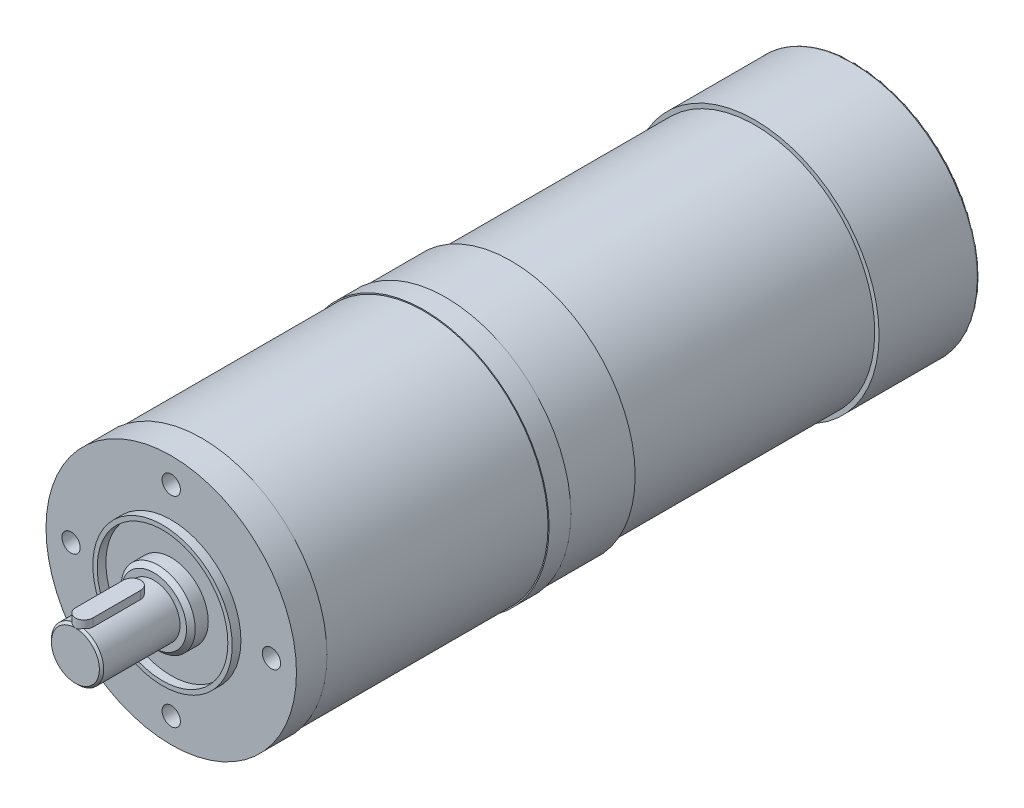
SolidWorks part; units mm, degrees
ref_plane "Plan de face" through (0, 0, 0) normal (0, 0, 1) x (1, 0, 0)
ref_plane "Plan de dessus" through (0, 0, 0) normal (0, 1, 0) x (1, 0, 0)
ref_plane "Plan de droite" through (0, 0, 0) normal (1, 0, 0) x (0, 0, -1)
sketch "Esquisse1" plane through (0, 0, 0) normal (0, 0, 1) x (1, 0, 0)
  circle A0 centre (0, 0) radius 28.5
  dimension "D1" = 57
extrude "Boss.-Extru.1" add sketch "Esquisse1" along normal blind 23
sketch "Esquisse3" plane through (0, 0, 23) normal (0, 0, 1) x (1, 0, 0)
  circle A0 centre (0, 0) radius 27.5
  dimension "D1" = 55
extrude "Boss.-Extru.2" add sketch "Esquisse3" along normal blind 56
sketch "Esquisse4" plane through (0, 0, 79) normal (0, 0, 1) x (1, 0, 0)
  circle A0 centre (0, 0) radius 28.5
  dimension "D1" = 57
extrude "Boss.-Extru.3" add sketch "Esquisse4" along normal blind 15
sketch "Esquisse5" plane through (0, 0, 94) normal (0, 0, 1) x (1, 0, 0)
  circle A0 centre (0, 0) radius 28.75
  dimension "D1" = 57.5
extrude "Boss.-Extru.4" add sketch "Esquisse5" along normal blind 5
sketch "Esquisse6" plane through (0, 0, 99) normal (0, 0, 1) x (1, 0, 0)
  circle A0 centre (0, 0) radius 28.5
  dimension "D1" = 57
extrude "Boss.-Extru.5" add sketch "Esquisse6" along normal blind 51
sketch "Esquisse7" plane through (0, 0, 150) normal (0, 0, 1) x (1, 0, 0)
  circle A0 centre (0, 0) radius 28.75
  circle A1 centre (0, 0) radius 28.75 construction
extrude "Boss.-Extru.6" add sketch "Esquisse7" along normal blind 7
fillet "Congé1" radius 0.5 1 edges at (28.5, 0, 0)
sketch "Esquisse8" plane through (0, 0, 157) normal (0, 0, 1) x (1, 0, 0)
  circle A0 centre (0, 0) radius 16
  circle A1 centre (0, 0) radius 15
  dimension "D1" = 32
  dimension "D2" = 1
extrude "Boss.-Extru.7" add sketch "Esquisse8" along normal blind 2
sketch "Esquisse9" plane through (0, 0, 157) normal (0, 0, 1) x (1, 0, 0)
  circle A0 centre (0, 0) radius 8.5
  dimension "D1" = 17
extrude "Boss.-Extru.8" add sketch "Esquisse9" along normal blind 4
chamfer "Chanfrein1" distance 1 angle 45 1 edges at (8.5, 0, 161)
sketch "Esquisse10" plane through (0, 0, 161) normal (0, 0, 1) x (1, 0, 0)
  circle A0 centre (0, 0) radius 6
  dimension "D1" = 12
extrude "Boss.-Extru.9" add sketch "Esquisse10" along normal blind 18
chamfer "Chanfrein2" distance 0.5 angle 45 1 edges at (6, 0, 179)
ref_plane "Plan1" through (0, 6, 0) normal (0, 1, 0) x (1, 0, 0)
sketch "Esquisse11" plane through (0, 6, 0) normal (0, 1, 0) x (1, 0, 0)
  line L0 (0, -184.2957) -> (0, -160.349) construction
  line L1 (0, -177) -> (0, -166) construction
  line L2 (-2, -177) -> (-2, -166)
  line L3 (2, -177) -> (2, -166)
  line L4 (-5.5, -179) -> (5.5, -179) construction
  line L6 (-5.0719, -164) -> (4.5645, -164) construction
  arc A0 (-2, -177) -> (2, -177) centre (0, -177) ccw
  arc A1 (2, -166) -> (-2, -166) centre (0, -166) ccw
  point P5 (0, -171.5)
  dimension "D1" = 4
  dimension "D2" = 15
extrude "Boss.-Extru.10" add sketch "Esquisse11" along normal blind 1.5 and the other way blind 1
hole_wizard "Trou pour taraudage pour trou taraudé M51" positions "Esquisse13" profile "Esquisse12" hole size "M5" standard "ISO"
sketch "Esquisse13" plane through (0, 0, 157) normal (0, 0, 1) x (1, 0, 0)
  line L0 (0, 0) -> (-36.1827, 0) construction
  circle A0 centre (0, 0) radius 23 construction
  point P0 (-23, 0)
  dimension "D1" = 46
sketch "Esquisse12" plane through (-23, 0, 157) normal (1, 0, 0) x (0, -1, 0)
  line L0 (0, 0) -> (0, 8.2618)
  line L1 (0, 8.2618) -> (2.1, 7)
  line L2 (2.1, 7) -> (2.1, 0)
  line L5 (2.1, 0) -> (0, 0)
  line L10 (0, 8.2618) -> (-2.1, 7) construction
  line L11 (0, -6.35) -> (0, 107.95) construction
  dimension "Diamètre du perçage" = 4.2
  dimension "Profondeur du perçage" = 7
  dimension "Angle de pointe" = 118
ref_axis "Axe1" through (0, 0, 178.5) along (0, 0, -1)
pattern_circular "Répétition circulaire1" count 4 over 360 about axis through (0, 0, 178.5) along (0, 0, -1) of "Trou pour taraudage pour trou taraudé M51"
